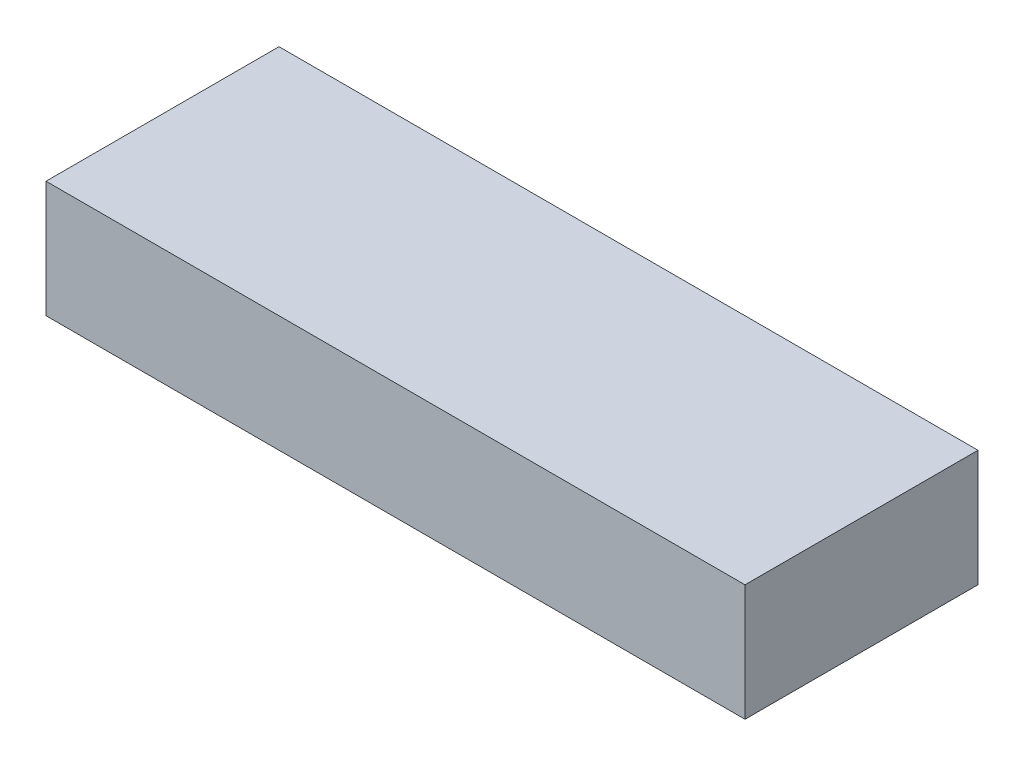
SolidWorks part; units mm, degrees
material "自定义塑料"
ref_plane "前视基准面" through (0, 0, 0) normal (0, 0, 1) x (1, 0, 0)
ref_plane "上视基准面" through (0, 0, 0) normal (0, 1, 0) x (1, 0, 0)
ref_plane "右视基准面" through (0, 0, 0) normal (1, 0, 0) x (0, 0, -1)
other "Configuration Table"
sketch "草图1" plane through (0, 0, 0) normal (0, 1, 0) x (1, 0, 0)
  line L1 (-90, -30) -> (90, -30)
  line L2 (-90, -30) -> (-90, 30)
  line L3 (-90, 30) -> (90, 30)
  line L4 (90, -30) -> (90, 30)
  line L5 (-90, -30) -> (90, 30) construction
  line L6 (-90, 30) -> (90, -30) construction
  point P0 (0, 0)
  dimension "D1" = 60
  dimension "D2" = 180
extrude "凸台-拉伸1" add sketch "草图1" along normal blind 15 and the other way blind 15
